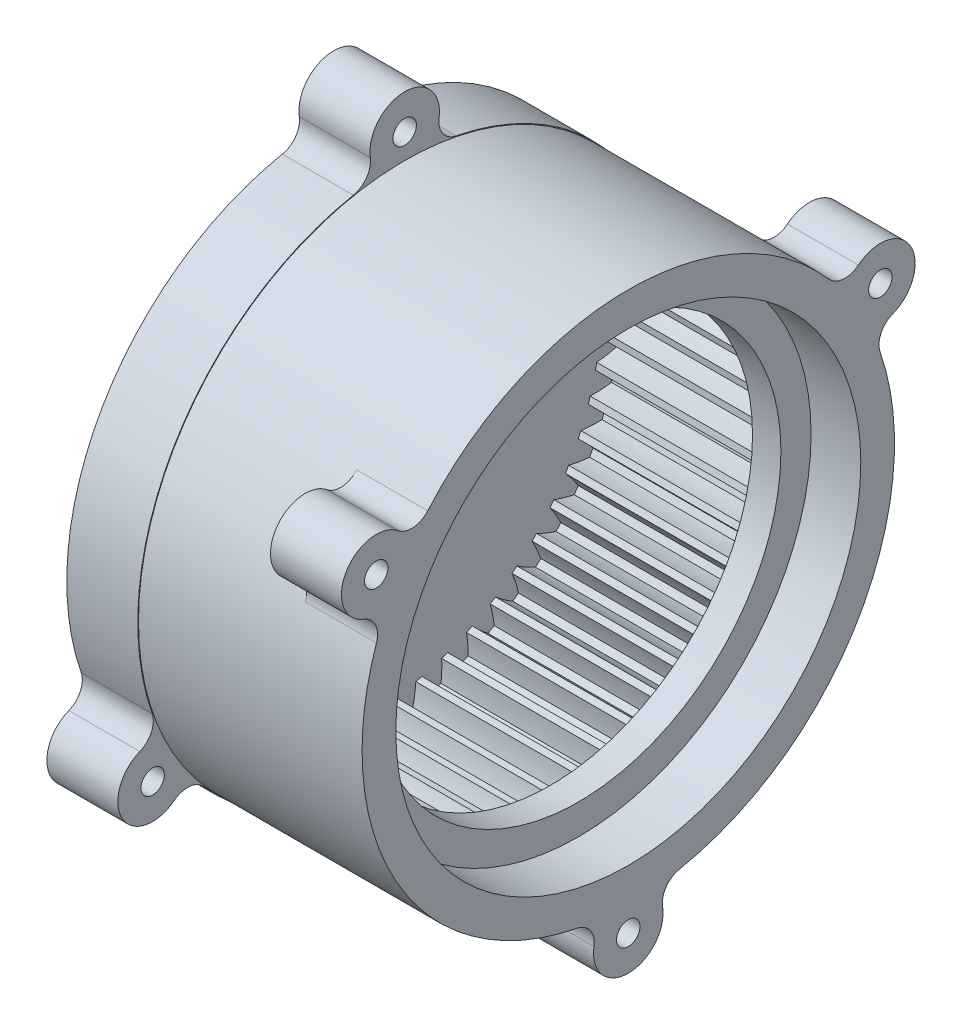
SolidWorks part; units mm, degrees
ref_plane "Plane1" through (0, 0, 0) normal (0, 0, 1) x (1, 0, 0)
ref_plane "Plane2" through (0, 0, 0) normal (0, 1, 0) x (1, 0, 0)
ref_plane "Plane3" through (0, 0, 0) normal (1, 0, 0) x (0, 0, -1)
sketch "HoldingSke" plane through (0, 0, 0) normal (0, 1, 0) x (1, 0, 0)
  line L0 (0, 0) -> (0.4589, -0.6553)
  line L1 (-15, 0) -> (100, 0) construction
  line L2 (0, 0) -> (-2.1039, 2.3779)
  line L3 (0, 0) -> (-11.863, 4.5341)
  line L4 (0, 0) -> (4.9534, 7.0742)
  line L5 (0, 0) -> (-23.7986, -8.8762)
  line L6 (0, 0) -> (-10.5278, -7.1032)
  line L7 (-2.1039, 2.3779) -> (3.3635, 27.1825)
  line L8 (-76.2, 3.6279) -> (-54.61, 3.6279)
  line L9 (-67.7845, 28.3722) -> (-49.3413, 33.142)
  line L10 (-76.2, 71.12) -> (104.1128, 71.12)
  line L11 (0, 0) -> (-26, 0)
  line L12 (-76.2, 101.6) -> (-76.155, 101.6)
  line L13 (24.9733, 27.94) -> (52.9518, 28.4284)
  line L14 (24.9733, 27.94) -> (24.9743, 27.94)
  line L15 (24.9733, 27.94) -> (100.4006, 29.5858)
  circle A0 centre (0, 0) radius 37.5
  circle A1 centre (0, 0) radius 12.7
  circle A2 centre (0, 0) radius 12.7
  dimension "MHD" = 25.4
  dimension "Hub_dia" = 25.4
  dimension "Diameter" = 75
  dimension "Num_teeth" = 55
  dimension "Pitch" = 0.8
  dimension "Overall_len" = 25.4
  dimension "Show_teeth" = 55
  dimension "Thickness" = 12.7
  dimension "OAL" = 25.4001
  dimension "T_dim" = 21.59
  dimension "Ap" = 14.5
  dimension "H" = 19.05
  dimension "Pitch_radius" = 180.3128
  dimension "Width" = 26
  dimension "Backlash" = 0.045
  dimension "Addendum_fac" = 1
  dimension "Dedendum_fac" = 1.25
  dimension "Clearance_fac" = 0.25
  dimension "Dedendum_add" = 0.001
  dimension "Module" = 1.25
sketch "BasProSke" plane through (0, 0, 0) normal (0, 1, 0) x (1, 0, 0)
  line L0 (-10, 0) -> (60, 0) construction
  line L1 (0, 33.125) -> (0, 37.5)
  line L2 (0, 33.125) -> (26, 33.125)
  line L3 (26, 33.125) -> (26, 37.5)
  line L4 (26, 37.5) -> (0, 37.5)
  dimension "Diameter" = 75
  dimension "Thickness" = 26
  dimension "Inside_diameter" = 66.25
revolve "Base-Revolve" add sketch "BasProSke" angle 360 about L0
sketch "TooCutSke" plane through (0, 0, 0) normal (1, 0, 0) x (0, 0, -1)
  line L3 (1.0941, 34.3576) -> (1.0941, 53.6633) construction
  line L4 (0, 0) -> (0, 59.563) construction
  line L5 (0, 0) -> (-3.9007, 68.2161) construction
  line L6 (-15.2783, 29.1274) -> (36.0712, 32.0636) construction
  circle A0 centre (0, 0) radius 34.375 construction
  circle A1 centre (0, 0) radius 35.9385 construction
  circle A2 centre (0, 0) radius 29.9521 construction
  circle A3 centre (0, 0) radius 33.0996 construction
  arc A4 (1.4514, 33.0678) -> (0.5036, 35.935) centre (-15.2783, 29.1274) ccw
  arc A5 (1.4514, 33.0678) -> (-1.4514, 33.0678) centre (0, 0) ccw
  arc A6 (0.5036, 35.935) -> (-0.5036, 35.935) centre (0, 0) ccw
  arc A7 (-0.5036, 35.935) -> (-1.4514, 33.0678) centre (15.2783, 29.1274) ccw
  dimension "Pitch_dia" = 68.75
  dimension "Base_dia" = 59.9041
  dimension "Root_dia" = 71.877
  dimension "Overcut_dia" = 66.1992
  dimension "Flank_rad" = 17.1875
  dimension "Half_ang" = 3.273
  dimension "Half_CT" = 1.0941
extrude "ToothCut" cut sketch "TooCutSke" along normal through all
fillet "Breaks" [suppressed] radius 0.125
fillet "RootFillets" [suppressed] radius 0.3135
pattern_circular "TeethCuts" count 55 every 6.545 about axis through (-10, 0, 0) along (1, 0, 0) of "RootFillets", "Breaks", "ToothCut"
sketch "Sketch2" plane through (0, 0, 0) normal (-1, 0, 0) x (0, 0, 1)
  circle A0 centre (0, 0) radius 37.5
extrude "Boss-Extrude2" add sketch "Sketch2" along normal blind 4.5
sketch "Sketch3" plane through (-4.5, 0, 0) normal (-1, 0, 0) x (0, 0, 1)
  line L0 (0, 0) -> (0, 8.5) construction
  line L1 (0, 0) -> (7.536, 0) construction
  circle A0 centre (0, 0) radius 2.25
  circle A1 centre (0, 8.5) radius 1.8
  circle A2 centre (0, -8.5) radius 1.8
  dimension "D1" = 4.5
  dimension "D2" = 3.6
extrude "Cut-Extrude1" cut sketch "Sketch3" against normal blind 4.5
sketch "Sketch4" plane through (0, 0, 0) normal (1, 0, 0) x (0, 0, -1)
  circle A0 centre (0, -8.5) radius 3.25
  circle A1 centre (0, 8.5) radius 3.25
  dimension "D1" = 6.5
extrude "Cut-Extrude2" cut sketch "Sketch4" against normal blind 3
sketch "Sketch5" plane through (26, 0, 0) normal (1, 0, 0) x (0, 0, -1)
  circle A0 centre (0, 0) radius 37.5
  circle A1 centre (0, 0) radius 28.5
  dimension "D1" = 57
extrude "Boss-Extrude3" add sketch "Sketch5" along normal blind 4
sketch "Sketch6" plane through (30, 0, 0) normal (1, 0, 0) x (0, 0, -1)
  circle A0 centre (0, 0) radius 37.5
  circle A1 centre (0, 0) radius 32.75
  dimension "D1" = 65.5
extrude "Boss-Extrude4" add sketch "Sketch6" along normal blind 7
sketch "Sketch7" plane through (37, 0, 0) normal (1, 0, 0) x (0, 0, -1)
  line L0 (0, 0) -> (0, -41) construction
  line L1 (0, 0) -> (0, -45.9) construction
  circle A0 centre (0, -41) radius 1.65
  circle A1 centre (-35.507, 20.5) radius 1.65
  circle A2 centre (35.507, 20.5) radius 1.65
  arc A4 (3.2765, -37.3566) -> (-3.2765, -37.3566) centre (0, -41) cw
  arc A5 (-33.99, 15.8408) -> (-30.7135, 21.5158) centre (-35.507, 20.5) cw
  arc A6 (30.7135, 21.5158) -> (33.99, 15.8408) centre (35.507, 20.5) cw
  circle A7 centre (0, 0) radius 37.5
  point P10 (0, 0)
  point P22 (0, 0)
  point P23 (0, 0)
  dimension "D2" = 3.3
  dimension "D1" = 41
  dimension "D4" = 3
  dimension "D3" = 3
extrude "Boss-Extrude5" add sketch "Sketch7" against normal blind 10
fillet "Fillet1" radius 3 6 edges at (32, 21.5158, 30.7135) (32, 15.8408, 33.99) (32, -37.3566, 3.2765) (32, -37.3566, -3.2765) (32, 15.8408, -33.99) (32, 21.5158, -30.7135)
sketch "Sketch8" plane through (-4.5, 0, 0) normal (-1, 0, 0) x (0, 0, 1)
  line L0 (0, 0) -> (0, 41) construction
  line L1 (0, 41) -> (0, 45.9) construction
  circle A2 centre (-35.507, -20.5) radius 1.65
  circle A3 centre (0, 41) radius 1.65
  arc A4 (-3.278, 37.3557) -> (3.275, 37.3557) centre (-0.0015, 40.9991) cw
  circle A5 centre (0, 0) radius 37.5
  circle A6 centre (0.0015, 0.0009) radius 37.5
  circle A7 centre (35.507, -20.5) radius 1.65
  circle A8 centre (0.0015, -0.0009) radius 37.5
  arc A9 (-30.712, -21.5167) -> (-33.9885, -15.8416) centre (-35.5055, -20.5009) cw
  arc A10 (33.99, -15.839) -> (30.7135, -21.5141) centre (35.507, -20.4983) cw
  point P13 (0, 0)
  point P28 (0.001, 0)
  point P29 (0, 0)
  dimension "D2" = 3
  dimension "D1" = 41
  dimension "D4" = 3
extrude "Boss-Extrude6" add sketch "Sketch8" against normal blind 10
fillet "Fillet2" radius 3 2 edges at (0.5, -15.8412, -33.9898) (0.5, -21.5177, -30.7122)
sketch "Sketch9" plane through (-4.5, 0, 0) normal (-1, 0, 0) x (0, 0, 1)
  circle A0 centre (0, 0) radius 37.6
  circle A1 centre (0, 0) radius 37.5
extrude "Boss-Extrude7" add sketch "Sketch9" against normal blind 10
fillet "Fillet3" radius 3 4 edges at (0.5, 37.4482, 3.375) (0.5, 37.448, -3.3778) (0.5, -15.7987, 34.1198) (0.5, -21.647, 30.7436)
equation "' \"Module@HoldingSke\" = 6.35"
equation "' \"Num_teeth@HoldingSke\" = 24"
equation "' \"Ap@HoldingSke\" =  14.5"
equation "' \"Ap@HoldingSke\" = 14.5"
equation "' \"Width@HoldingSke\" = 12"
equation "' \"Diameter@HoldingSke\" = 8 * 25.4"
equation "' \"Show_teeth@HoldingSke\" = 100"
equation "' \"Backlash@HoldingSke\" = 0.009 * 25.4"
equation "' \"Addendum_fac@HoldingSke\" = 1.0"
equation "' \"Dedendum_fac@HoldingSke\" = 1.25"
equation "' \"Dedendum_add@HoldingSke\" = 0.00005 * 25.4"
equation "' \"Clearance_fac@HoldingSke\" = 0.25"
equation "\"Pitch@HoldingSke\" = 1 / \"Module@HoldingSke\" "
equation "\"Overcut_dia@TooCutSke\" = (\"Num_teeth@HoldingSke\" - 2 * \"Addendum_fac@HoldingSke\") / \"Pitch@HoldingSke\" - 0.002 * 25.4"
equation "\"Pitch_dia@TooCutSke\" = \"Num_teeth@HoldingSke\" / \"Pitch@HoldingSke\""
equation "\"Base_dia@TooCutSke\" = \"Num_teeth@HoldingSke\" / \"Pitch@HoldingSke\" * cos((\"Ap@HoldingSke\"  * 3.14159265 / 180)) * 0.90"
equation "\"Root_dia@TooCutSke\" = \"Num_teeth@HoldingSke\"  / \"Pitch@HoldingSke\" + 2 *  \"Dedendum_fac@HoldingSke\"/ \"Pitch@HoldingSke\" + \"Dedendum_add@HoldingSke\" * 2"
equation "\"Half_ang@TooCutSke\" = 180 / \"Num_teeth@HoldingSke\""
equation "\"Half_CT@TooCutSke\" = \"Num_teeth@HoldingSke\" / \"Pitch@HoldingSke\" * sin((3.14159265 / 2 / \"Num_teeth@HoldingSke\")) / 2 + 10 * \"Backlash@HoldingSke\" / 4"
equation "\"Flank_rad@TooCutSke\" = \"Num_teeth@HoldingSke\" / \"Pitch@HoldingSke\" / 4"
equation "\"Radius@RootFillets\"= \"Clearance_fac@HoldingSke\" / \"Pitch@HoldingSke\" + \"Dedendum_add@HoldingSke\""
equation "\"Break_rad@Breaks\" = 0.02 / \"Pitch@HoldingSke\" * 5"
equation "\"Num_teeth@TeethCuts\" = int( \"Show_teeth@HoldingSke\" ) + 1"
equation "\"Num_teeth@TeethCuts\" = ((sgn( \"Num_teeth@TeethCuts\" - \"Num_teeth@HoldingSke\" )-1)*( \"Num_teeth@TeethCuts\" - \"Num_teeth@HoldingSke\" ))/-2+ \"Num_teeth@HoldingSke\""
equation "\"Num_teeth@TeethCuts\" = ((sgn( \"Num_teeth@TeethCuts\" - 2.0)+1)*( \"Num_teeth@TeethCuts\" - 2.0))/2 +2.0"
equation "\"Angle@TeethCuts\" = 360.0 / \"Num_teeth@HoldingSke\""
equation "\"Diameter@BasProSke\" = \"Num_teeth@HoldingSke\"  / \"Pitch@HoldingSke\" + 2 *  \"Dedendum_fac@HoldingSke\"/ \"Pitch@HoldingSke\" + \"Dedendum_add@HoldingSke\" * 2 + 0.002 * 25.4"
equation "\"Diameter@BasProSke\" = ((sgn( \"Diameter@BasProSke\"  - \"Diameter@HoldingSke\" )+1)*( \"Diameter@BasProSke\"  - \"Diameter@HoldingSke\" ))/2 + \"Diameter@HoldingSke\""
equation "\"Inside_diameter@BasProSke\" =  (\"Num_teeth@HoldingSke\" - 2 * \"Addendum_fac@HoldingSke\") / \"Pitch@HoldingSke\" "
equation "\"Thickness@BasProSke\"  = \"Width@HoldingSke\""
